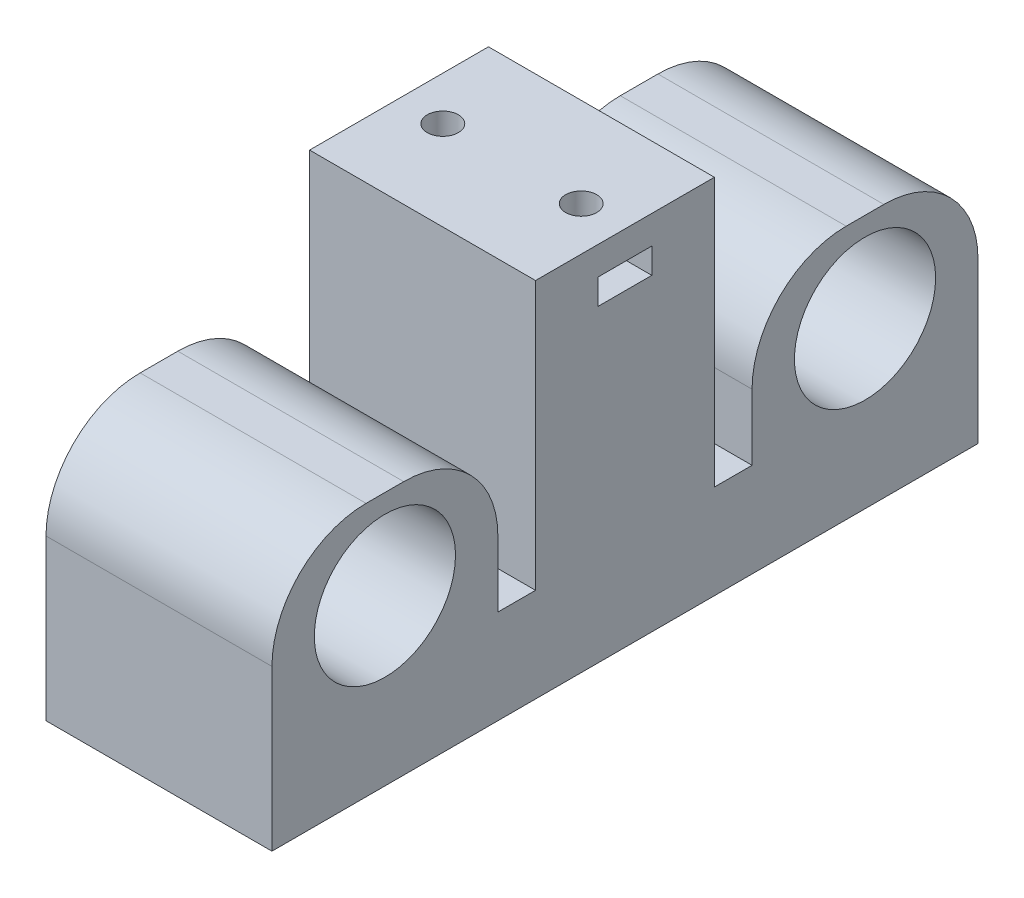
SolidWorks part; units mm, degrees
ref_plane "Front Plane" through (0, 0, 0) normal (0, 0, 1) x (1, 0, 0)
ref_plane "Top Plane" through (0, 0, 0) normal (0, 1, 0) x (1, 0, 0)
ref_plane "Right Plane" through (0, 0, 0) normal (1, 0, 0) x (0, 0, -1)
sketch "Sketch1" plane through (0, 0, 0) normal (0, 1, 0) x (1, 0, 0)
  line L1 (-24, 75) -> (0, 75)
  line L2 (-24, 75) -> (-24, 0)
  line L3 (-24, 0) -> (0, 0)
  line L4 (0, 75) -> (0, 0)
  dimension "D1" = 75
  dimension "D2" = 24
extrude "Boss-Extrude1" add sketch "Sketch1" along normal blind 10
sketch "Sketch2" plane through (0, 10, 0) normal (0, 1, 0) x (1, 0, 0)
  line L0 (-1024, 37.5) -> (48976, 37.5) construction
  line L1 (-24, 75) -> (-24, 0) construction
  line L2 (-1052.1461, 63) -> (48947.8539, 63) construction
  line L3 (-1043.7342, 12) -> (48956.2658, 12) construction
  line L4 (0, 0) -> (0, 75) construction
  line L6 (0, 75) -> (-24, 75) construction
  line L7 (-24, 0) -> (0, 0)
  line L8 (-24, 75) -> (0, 75)
  line L9 (-24, 75) -> (-24, 51)
  line L10 (-24, 51) -> (0, 51)
  line L11 (0, 75) -> (0, 51)
  line L12 (-24, 0) -> (-24, 24)
  line L13 (-24, 24) -> (0, 24)
  line L14 (0, 0) -> (0, 24)
  point P5 (-24, 37.5)
  dimension "D1" = 25.5
  dimension "D2" = 25.5
extrude "Boss-Extrude2" add sketch "Sketch2" along normal blind 17
sketch "Sketch3" plane through (0, 0, 0) normal (1, 0, 0) x (0, 0, -1)
  line L0 (12, -972) -> (12, 49028) construction
  line L1 (0, 27) -> (24, 27) construction
  line L2 (63, -972) -> (63, 49028) construction
  line L3 (51, 27) -> (75, 27) construction
  line L4 (24, 10) -> (51, 10) construction
  circle A0 centre (12, 17.5) radius 7.5
  circle A1 centre (63, 17.5) radius 7.5
  point P9 (12, 27)
  point P14 (63, 27)
  dimension "D1" = 15
extrude "Cut-Extrude1" cut sketch "Sketch3" against normal through all
fillet "Fillet1" radius 10 4 edges at (-12, 27, -51) (-12, 27, -24) (-12, 27, 0) (-12, 27, -75)
sketch "Sketch4" plane through (0, 10, 0) normal (0, 1, 0) x (1, 0, 0)
  line L0 (-1024, 37.5) -> (48976, 37.5) construction
  line L1 (-24, 51) -> (-24, 24) construction
  line L2 (0, 24) -> (0, 51) construction
  line L3 (0, 47) -> (-24, 47)
  line L4 (0, 47) -> (0, 28)
  line L5 (0, 28) -> (-24, 28)
  line L6 (-24, 47) -> (-24, 28)
  point P5 (-24, 37.5)
  dimension "D1" = 9.5
extrude "Boss-Extrude3" add sketch "Sketch4" along normal blind 28.5
sketch "Sketch5" plane through (-24, 0, 0) normal (-1, 0, 0) x (0, 0, 1)
  line L0 (-37.5, -961.5) -> (-37.5, 49038.5) construction
  line L1 (-40.35, 35.5) -> (-34.65, 35.5)
  line L2 (-40.35, 35.5) -> (-40.35, 32.8)
  line L3 (-40.35, 32.8) -> (-34.65, 32.8)
  line L4 (-34.65, 35.5) -> (-34.65, 32.8)
  line L5 (-47, 38.5) -> (-28, 38.5) construction
  point P9 (-37.5, 38.5)
  dimension "D1" = 5.7
  dimension "D2" = 2.7
  dimension "D3" = 3
extrude "Cut-Extrude2" cut sketch "Sketch5" against normal blind 11
extrude "Cut-Extrude3" cut sketch "Sketch5<2>" along normal blind 11 from surface starting at face at (0, 17.5, -70.5)
sketch "Sketch5<2>" plane through (-24, 0, 0) normal (-1, 0, 0) x (0, 0, 1) same geometry as "Sketch5"
sketch "Sketch6" plane through (0, 38.5, 0) normal (0, 1, 0) x (1, 0, 0)
  line L0 (-1024, 37.5) -> (48976, 37.5) construction
  line L1 (-24, 47) -> (-24, 28) construction
  line L2 (-12, -972) -> (-12, 49028) construction
  line L3 (-24, 28) -> (0, 28) construction
  line L4 (0, 28) -> (0, 47) construction
  circle A0 centre (-4.65, 37.5) radius 1.65
  circle A1 centre (-19.35, 37.5) radius 1.65
  point P9 (-24, 37.5)
  point P14 (-12, 28)
  dimension "D1" = 3.3
  dimension "D2" = 3
extrude "Cut-Extrude4" cut sketch "Sketch6" against normal up to next
